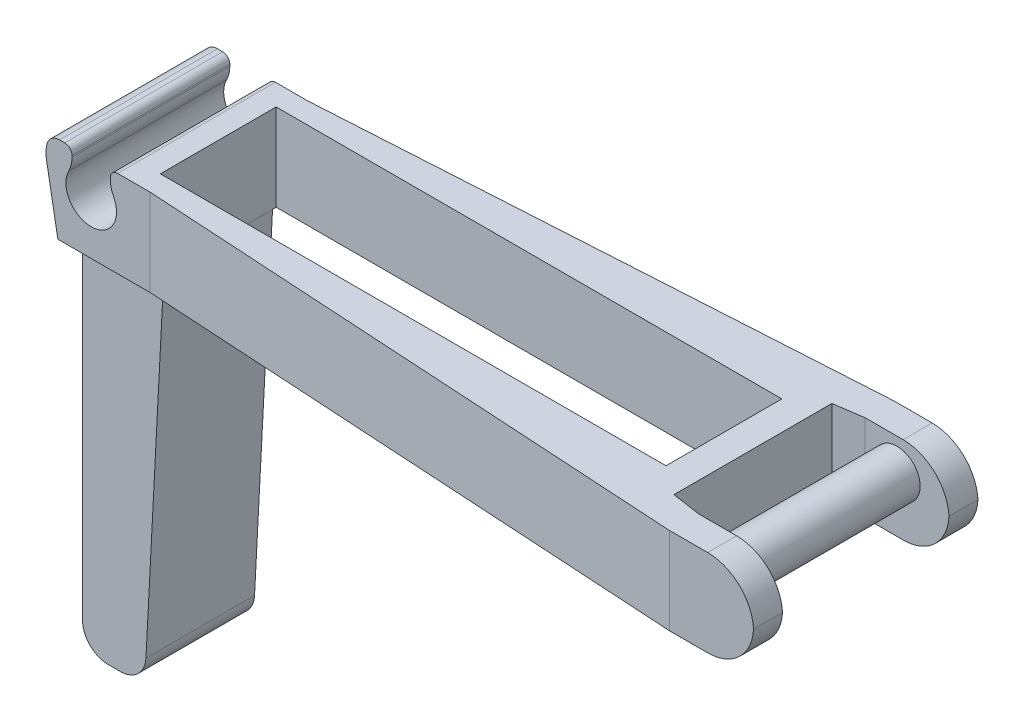
SolidWorks part; units mm, degrees
ref_plane "Front Plane" through (0, 0, 0) normal (0, 0, 1) x (1, 0, 0)
ref_plane "Top Plane" through (0, 0, 0) normal (0, 1, 0) x (1, 0, 0)
ref_plane "Right Plane" through (0, 0, 0) normal (1, 0, 0) x (0, 0, -1)
sketch "Sketch1" plane through (0, 0, 0) normal (0, 0, 1) x (1, 0, 0)
  line L0 (-24.05, 2.354) -> (-24.4097, 2.354)
  line L1 (-18.725, 2.354) -> (-20.4, 2.354)
  line L2 (-22.225, 0) -> (22.225, 0) construction
  line L3 (22.225, 0) -> (22.225, 0.15) construction
  line L4 (-23.55, 1.734) -> (-23.55, 1.854)
  line L5 (-20.9, 1.734) -> (-20.9, 1.854)
  line L6 (-24.525, -3.6477) -> (-25.3059, 0.6714)
  line L7 (-24.525, -3.6477) -> (18.025, -3.6477)
  line L8 (18.025, -3.6477) -> (18.025, 2.354)
  line L9 (18.025, 2.354) -> (-18.725, 2.354)
  line L10 (20.625, 0.15) -> (18.025, 0.15) construction
  arc A0 (-24.4097, 2.354) -> (-25.2894, 1.6441) centre (-24.4097, 1.454) ccw
  arc A1 (-20.4, 2.354) -> (-20.9, 1.854) centre (-20.4, 1.854) ccw
  arc A2 (-20.9, 1.734) -> (-20.6733, 0.8092) centre (-18.9, 1.734) ccw
  arc A3 (-23.55, 1.854) -> (-24.05, 2.354) centre (-24.05, 1.854) ccw
  arc A4 (-23.7767, 0.8092) -> (-23.55, 1.734) centre (-25.55, 1.734) ccw
  arc A5 (-23.7767, 0.8092) -> (-20.6733, 0.8092) centre (-22.225, 0) ccw
  arc A6 (20.625, 0.15) -> (21.4375, -1.2428) centre (22.225, 0.15) ccw
  arc A7 (21.4276, 1.5372) -> (20.625, 0.15) centre (22.225, 0.15) ccw
  arc A8 (21.4375, -1.2428) -> (21.4276, 1.5372) centre (22.225, 0.15) ccw
  arc A9 (-25.2894, 1.6441) -> (-25.3059, 0.6714) centre (-22.8458, 1.1162) ccw
  point P41 (0, 0)
  dimension "D1" = 1.75
  dimension "D2" = 1.6
  dimension "D4" = 0.5
  dimension "D6" = 2.5
  dimension "D10" = 0.9
  dimension "D3" = 0.12
  dimension "D5" = 1.675
  dimension "D7" = 4.3891
  dimension "D8" = 79.751
  dimension "D9" = 0.979
  dimension "D11" = 1.2223
  dimension "D12" = 0.3597
  dimension "D13" = 0.8797
  dimension "D14" = 0.8092
  dimension "D15" = 0.9248
  dimension "D16" = 0.15
  dimension "D17" = 2.6
  dimension "D18" = 6.0017
  dimension "D19" = 44.45
extrude "Boss-Extrude1" add sketch "Sketch1" along normal mid plane 10.9 contours A6 A8 A7 | L7 L8 L9 L1 A1 L5 A2 A5 A4 L4 A3 L0 A0 A9 L6 region at (22.225, 0.15, 0)
extrude "Boss-Extrude2" add sketch "Sketch1<4>" along normal mid plane 11.5 contours A8 A7 A6
sketch "Sketch1<4>" plane through (0, 0, 0) normal (0, 0, 1) x (1, 0, 0) same geometry as "Sketch1"
sketch "Sketch2" plane through (0, -3.6477, 0) normal (0, -1, 0) x (-1, 0, 0)
  line L0 (-25.825, 5.75) -> (-20.0177, 5.75)
  line L1 (-20.625, 5.75) -> (-23.825, 5.75) construction
  line L2 (-23.825, 5.75) -> (-23.825, -5.75) construction
  line L3 (-25.825, 5.75) -> (-25.825, 7.75)
  line L4 (-25.825, 7.75) -> (-20.0177, 7.75)
  line L5 (18.175, -5.45) -> (18.175, 5.45)
  line L7 (18.175, 5.45) -> (-20.0177, 7.75)
  line L8 (-20.0177, 5.75) -> (-18.025, 5.45)
  line L9 (-18.025, 5.45) -> (18.175, 0)
  line L10 (18.175, 0) -> (-30.5676, 0) construction
  line L11 (-18.025, -5.45) -> (18.175, 0)
  line L12 (-20.0177, -5.75) -> (-18.025, -5.45)
  line L13 (18.175, -5.45) -> (-20.0177, -7.75)
  line L14 (-25.825, -7.75) -> (-20.0177, -7.75)
  line L15 (-25.825, -5.75) -> (-25.825, -7.75)
  line L16 (-25.825, -5.75) -> (-20.0177, -5.75)
  line L18 (24.525, 5.45) -> (-18.025, 5.45) construction
  line L19 (24.525, -5.45) -> (24.525, 5.45) construction
  line L20 (24.525, -5.45) -> (-18.025, -5.45) construction
  line M9 (24.525, 5.45) -> (-18.025, 5.45)
  line M11 (-18.025, -5.45) -> (24.525, -5.45)
  dimension "D1" = 2
  dimension "D2" = 2
  dimension "D3" = 6.35
extrude "Boss-Extrude3" add sketch "Sketch2" against normal up to surface (6.0017 mm away) contours L9 L5 M9 | L0 L8 L7 L4 L3 M9 | L11 L5 M11 | L16 L15 L14 L13 L12 M11 region at (10.5089, -3.6477, -6.3324) region at (-6.1083, -3.6477, 3.6333) region at (-6.1083, -3.6477, -3.6333) region at (10.5089, -3.6477, 6.3324) up to face at (-1.1875, 2.354, 0)
fillet "Fillet1" radius 3.175 4 edges at (25.825, 2.354, -6.75) (25.825, -3.6477, -6.75) (25.825, 2.354, 6.75) (25.825, -3.6477, 6.75)
sketch "Sketch3" plane through (0, -3.6477, 0) normal (0, -1, 0) x (-1, 0, 0)
  line L0 (24.525, -5.45) -> (24.525, 5.45) construction
  line L1 (18.9, -4) -> (-16.025, -4)
  line L2 (18.9, -4) -> (18.9, 4)
  line L3 (18.9, 4) -> (-16.025, 4)
  line L4 (-16.025, -4) -> (-16.025, 4)
  line L6 (-18.025, -5.45) -> (-18.025, 5.45) construction
  point P8 (18.9, 0)
  point P9 (24.525, 0)
  dimension "D1" = 8
  dimension "D2" = 34.925
  dimension "D3" = 2
extrude "Cut-Extrude1" cut sketch "Sketch3" against normal through all contours L2 L3 L4 L1
sketch "Sketch4" plane through (0, 0, 0) normal (0, 0, 1) x (1, 0, 0)
  line L0 (-18.9, -3.6477) -> (-20.2312, -29.0477)
  line L1 (-24.525, -3.6477) -> (-18.175, -3.6477) construction
  line L2 (-20.2312, -29.0477) -> (-24.525, -29.0477)
  line L3 (-24.525, -29.0477) -> (-24.525, -3.6477)
  line L4 (-24.525, -3.6477) -> (-18.9, -3.6477)
  dimension "D2" = 25.4
  dimension "D3" = 3
extrude "Boss-Extrude5" add sketch "Sketch4" along normal mid plane 7.5
fillet "Fillet2" radius 1.778 2 edges at (-20.2312, -29.0477, 0) (-24.525, -29.0477, 0)
